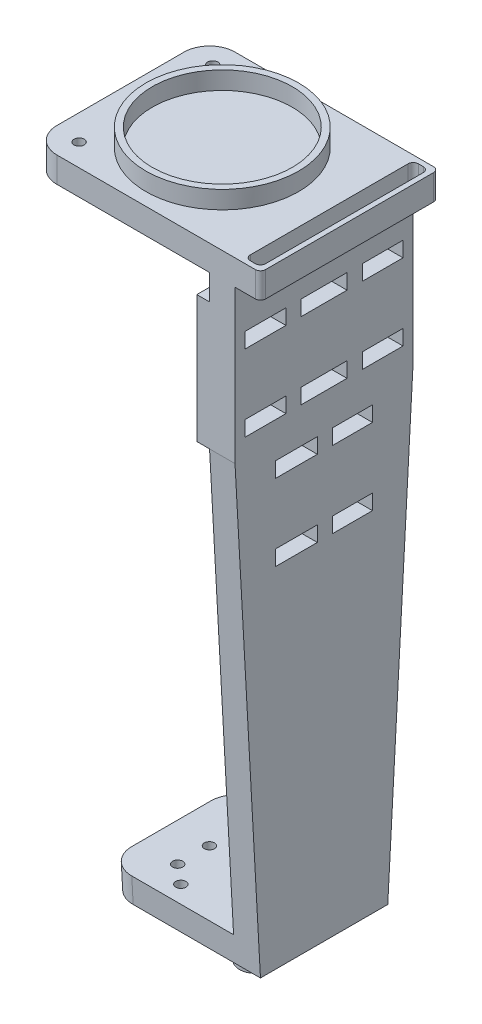
SolidWorks part; units mm, degrees
ref_plane "Front Plane" through (0, 0, 0) normal (0, 0, 1) x (1, 0, 0)
ref_plane "Top Plane" through (0, 0, 0) normal (0, 1, 0) x (1, 0, 0)
ref_plane "Right Plane" through (0, 0, 0) normal (1, 0, 0) x (0, 0, -1)
sketch "Sketch1" plane through (0, 0, 0) normal (0, 1, 0) x (1, 0, 0)
  line L1 (0, 0) -> (-80, 0)
  line L2 (0, 0) -> (0, -70)
  line L3 (0, -70) -> (-80, -70)
  line L4 (-80, 0) -> (-80, -70)
  dimension "D1" = 80
  dimension "D2" = 70
extrude "Boss-Extrude1" add sketch "Sketch1" along normal blind 10
sketch "Sketch2" plane through (0, 0, 0) normal (0, -1, 0) x (1, 0, 0)
  line L0 (0, 0) -> (-80, 0) construction
  line L1 (0, 70) -> (-10, 70)
  line L2 (0, 70) -> (0, 0)
  line L3 (0, 0) -> (-10, 0)
  line L4 (-10, 70) -> (-10, 0)
  dimension "D1" = 10
extrude "Boss-Extrude2" add sketch "Sketch2" along normal blind 450
sketch "Sketch3" plane through (0, 10, 0) normal (0, 1, 0) x (1, 0, 0)
  line L0 (0, 0) -> (-80, -70) construction
  line L1 (-80, -70) -> (-80, 0) construction
  line L2 (-80, 0) -> (0, -70) construction
  line L3 (0, -70) -> (0, 0) construction
  line L4 (0, 0) -> (-80, 0) construction
  line L5 (-80, 0) -> (-80, -70) construction
  line L6 (-80, -70) -> (0, -70) construction
  circle A0 centre (-40, -35) radius 27.5
  circle A1 centre (-40, -35) radius 30
  dimension "D1" = 55
  dimension "D2" = 60
extrude "Boss-Extrude3" add sketch "Sketch3" along normal blind 7
sketch "Sketch6" plane through (0, 10, 0) normal (0, 1, 0) x (1, 0, 0)
  line L0 (-80, -70) -> (-80, -35) construction
  line L1 (-80, 0) -> (-80, -70) construction
  line L2 (-80, -35) -> (-40, -70) construction
  line L3 (-80, -70) -> (0, -70) construction
  line L4 (-40, -70) -> (-80, -70) construction
  line L5 (-80, -70) -> (-80, -35) construction
  line L6 (-80, -35) -> (-80, 0) construction
  line L7 (-80, 0) -> (-40, 0) construction
  line L8 (0, 0) -> (-80, 0) construction
  line L9 (-40, 0) -> (-80, -35) construction
  line L10 (-80, -52.5) -> (-60, -70) construction
  line L11 (-80, -17.5) -> (-60, 0) construction
  circle A0 centre (-70, -61.25) radius 2
  circle A1 centre (-70, -8.75) radius 2
  dimension "D1" = 4
  dimension "D2" = 4
extrude "Cut-Extrude3" cut sketch "Sketch6" against normal blind 27
sketch "Sketch7" plane through (-10, 0, 0) normal (-1, 0, 0) x (0, 0, 1)
  line L0 (70, -450) -> (70, 0) construction
  line L1 (0, -450) -> (70, -450)
  line L2 (0, -450) -> (0, -240)
  line L3 (0, -240) -> (70, -240)
  line L4 (70, -450) -> (70, -240)
  dimension "D1" = 210
extrude "Cut-Extrude4" cut sketch "Sketch7" against normal blind 27
sketch "Sketch10" plane through (-10, 0, 0) normal (-1, 0, 0) x (0, 0, 1)
  line L0 (0, 0) -> (0, -120) construction
  line L1 (0, -240) -> (0, 0) construction
  line L2 (0, -120) -> (70, -120) construction
  line L3 (70, -240) -> (70, 0) construction
  line L4 (70, -120) -> (70, 0) construction
  line L5 (70, 0) -> (0, 0) construction
  line L6 (0, 0) -> (70, -120) construction
  line L7 (70, 0) -> (0, -120) construction
  line L8 (0, -240) -> (70, -240) construction
  line L9 (70, -240) -> (35, -240) construction
  line L10 (35, -240) -> (0, -240) construction
  line L11 (0, -60) -> (10, -240)
  line L12 (0, -240) -> (0, -60)
  line L13 (70, -60) -> (60, -240)
  line L14 (60, -240) -> (70, -240)
  line L15 (70, -240) -> (70, -60)
  line L16 (0, -240) -> (10, -240)
  dimension "D1" = 10
  dimension "D2" = 10
extrude "Cut-Extrude5" cut sketch "Sketch10" against normal blind 70
sketch "Sketch11" plane through (-10, 0, 0) normal (-1, 0, 0) x (0, 0, 1)
  line L0 (10.1166, -240) -> (60, -240)
  line L1 (60, -240) -> (10, -240) construction
  line L2 (60, -240) -> (60.5556, -230)
  line L3 (70, -60) -> (60, -240) construction
  line L4 (60.5556, -230) -> (9.4444, -230)
  line L5 (10, -240) -> (0, -60) construction
  line L6 (9.4444, -230) -> (10.1166, -240)
  dimension "D1" = 10
extrude "Boss-Extrude5" add sketch "Sketch11" along normal blind 50
sketch "Sketch12" plane through (0, -240, 0) normal (0, -1, 0) x (1, 0, 0)
  line L0 (-60, 60) -> (0, 10) construction
  line L1 (0, 10) -> (0, 60) construction
  line L2 (0, 60) -> (-60, 10.1166) construction
  circle A0 centre (-30, 35) radius 7.5
  circle A1 centre (-30, 35) radius 10
  circle A2 centre (-30, 35) radius 2.5
  dimension "D1" = 15
  dimension "D2" = 20
  dimension "D3" = 5
extrude "Boss-Extrude6" add sketch "Sketch12" along normal blind 25 contours A2 | A1 A0 region at (-39.7172, -240, 35) region at (-30, -240, 35)
sketch "Sketch13" plane through (0, -240, 0) normal (0, -1, 0) x (-1, 0, 0)
  line L0 (60, -60) -> (0, -60) construction
  line L1 (0, -60) -> (0, -10) construction
  line L2 (0, -10) -> (60, -10.1166) construction
  line L3 (60, -10.1166) -> (60, -60) construction
  line L4 (60, -60) -> (30, -60) construction
  line L5 (30, -60) -> (0, -60) construction
  line L6 (0, -60) -> (0, -35) construction
  line L7 (0, -35) -> (0, -10) construction
  line L8 (0, -10) -> (30, -10.0583) construction
  line L9 (30, -10.0583) -> (60, -10.1166) construction
  line L10 (60, -10.1166) -> (60, -35.0583) construction
  line L11 (60, -35.0583) -> (60, -60) construction
  line L12 (60, -35.0583) -> (30, -60) construction
  line L13 (30, -60) -> (0, -35) construction
  line L14 (0, -35) -> (30, -10.0583) construction
  line L15 (30, -10.0583) -> (60, -35.0583) construction
  line L16 (45, -47.5291) -> (45, -60) construction
  line L17 (45, -60) -> (45, -10.0874) construction
  line L18 (45, -47.5291) -> (15, -47.5) construction
  line L19 (15, -47.5) -> (15, -22.5291) construction
  line L20 (15, -22.5291) -> (45, -22.5583) construction
  line L21 (45, -47.5291) -> (30, -60) construction
  line L22 (30, -60) -> (45, -47.5291) construction
  line L23 (45, -47.5291) -> (37.5, -53.7646) construction
  line L24 (37.5, -53.7646) -> (37.5, -16.3083) construction
  circle A0 centre (45, -47.5291) radius 2
  circle A1 centre (45, -22.5583) radius 2
  circle A2 centre (45, -35.0437) radius 2
  circle A3 centre (37.5, -53.7646) radius 2
  circle A4 centre (37.5, -16.3083) radius 2
  dimension "D1" = 4
  dimension "D2" = 4
  dimension "D3" = 4
  dimension "D4" = 4
  dimension "D5" = 4
extrude "Cut-Extrude6" cut sketch "Sketch13" against normal blind 25
sketch "Sketch14" plane through (-10, 0, 0) normal (-1, 0, 0) x (0, 0, 1)
  line L1 (0, -60) -> (24, -60)
  line L2 (0, -60) -> (0, -10)
  line L3 (0, -10) -> (24, -10)
  line L4 (24, -60) -> (24, -10)
  line L5 (2, -12) -> (22, -12)
  line L6 (2, -12) -> (2, -58)
  line L7 (2, -58) -> (22, -58)
  line L8 (22, -12) -> (22, -58)
  dimension "D1" = 50
  dimension "D2" = 24
  dimension "D3" = 2
  dimension "D4" = 2
  dimension "D5" = 2
  dimension "D6" = 2
extrude "Boss-Extrude7" add sketch "Sketch14" along normal blind 5
sketch "Sketch15" plane through (-10, 0, 0) normal (-1, 0, 0) x (0, 0, 1)
  line L1 (70, -60) -> (46, -60)
  line L2 (70, -60) -> (70, -10)
  line L3 (70, -10) -> (46, -10)
  line L4 (46, -60) -> (46, -10)
  line L5 (68, -58) -> (48, -58)
  line L6 (68, -58) -> (68, -12)
  line L7 (68, -12) -> (48, -12)
  line L8 (48, -58) -> (48, -12)
  dimension "D1" = 50
  dimension "D2" = 24
  dimension "D3" = 2
  dimension "D4" = 2
  dimension "D5" = 2
  dimension "D6" = 2
extrude "Boss-Extrude8" add sketch "Sketch15" along normal blind 5
sketch "Sketch16" plane through (-10, 0, 0) normal (-1, 0, 0) x (0, 0, 1)
  line L1 (24, -10) -> (46, -10)
  line L2 (24, -10) -> (24, -60)
  line L3 (24, -60) -> (46, -60)
  line L4 (46, -10) -> (46, -60)
  line L5 (24, -12) -> (46, -12)
  line L6 (24, -12) -> (24, -58)
  line L7 (24, -58) -> (46, -58)
  line L8 (46, -12) -> (46, -58)
  line M6 (24, -10) -> (24, -60)
  line M12 (46, -60) -> (46, -10)
  dimension "D1" = 2
  dimension "D2" = 2
extrude "Boss-Extrude9" add sketch "Sketch16" along normal blind 5 contours L5 L4 L1 M6 | L7 L3 M6 M12 region at (-10, -11, 35) region at (-10, -59, 35)
sketch "Sketch17" plane through (-10, 0, 0) normal (-1, 0, 0) x (0, 0, 1)
  line L0 (0, -60) -> (70, -60) construction
  line L1 (70, -60) -> (35, -60) construction
  line L2 (35, -60) -> (0, -60) construction
  line L3 (12, -12) -> (12, -60) construction
  line L4 (22, -12) -> (2, -12) construction
  line L5 (58, -12) -> (58, -60) construction
  line L6 (68, -12) -> (48, -12) construction
  line L7 (12, -60) -> (58, -60)
  line L8 (58, -60) -> (58, -110)
  line L9 (58, -110) -> (12, -110)
  line L10 (12, -110) -> (12, -60)
  line L12 (14, -62) -> (33.659, -62)
  line L13 (14, -62) -> (14, -108)
  line L14 (14, -108) -> (33.659, -108)
  line L15 (33.659, -62) -> (33.659, -108)
  line L16 (35.659, -62) -> (56, -62)
  line L17 (35.659, -62) -> (35.659, -108)
  line L18 (35.659, -108) -> (56, -108)
  line L19 (56, -62) -> (56, -108)
  dimension "D1" = 50
  dimension "D2" = 2
  dimension "D3" = 2
  dimension "D4" = 2
  dimension "D5" = 2
  dimension "D6" = 2
  dimension "D7" = 2
  dimension "D8" = 2
extrude "Boss-Extrude10" add sketch "Sketch17" along normal blind 5
sketch "Sketch18" plane through (-10, 0, 0) normal (-1, 0, 0) x (0, 0, 1)
  line L0 (2, -12) -> (2, -58) construction
  line L1 (4, -17) -> (20, -17)
  line L2 (4, -17) -> (4, -23)
  line L3 (4, -23) -> (20, -23)
  line L4 (20, -17) -> (20, -23)
  line L5 (26, -17) -> (44, -17)
  line L6 (26, -17) -> (26, -23)
  line L7 (26, -23) -> (44, -23)
  line L8 (44, -17) -> (44, -23)
  line L9 (50, -17) -> (66, -17)
  line L10 (50, -17) -> (50, -23)
  line L11 (50, -23) -> (66, -23)
  line L12 (66, -17) -> (66, -23)
  line L13 (4, -47) -> (20, -47)
  line L14 (4, -47) -> (4, -53)
  line L15 (4, -53) -> (20, -53)
  line L16 (20, -47) -> (20, -53)
  line L17 (26, -47) -> (44, -47)
  line L18 (26, -47) -> (26, -53)
  line L19 (26, -53) -> (44, -53)
  line L20 (44, -47) -> (44, -53)
  line L21 (50, -47) -> (66, -47)
  line L22 (50, -47) -> (50, -53)
  line L23 (50, -53) -> (66, -53)
  line L24 (66, -47) -> (66, -53)
  line L25 (22, -58) -> (22, -12) construction
  line L26 (22, -12) -> (2, -12) construction
  line L27 (2, -58) -> (22, -58) construction
  line L28 (24, -58) -> (24, -12) construction
  line L29 (24, -12) -> (46, -12) construction
  line L30 (24, -58) -> (46, -58) construction
  line L31 (48, -58) -> (68, -58) construction
  line L32 (68, -12) -> (48, -12) construction
  line L33 (46, -12) -> (46, -58) construction
  line L34 (68, -58) -> (68, -12) construction
  line L35 (48, -12) -> (48, -58) construction
  point P28 (12, -12)
  dimension "D1" = 2
  dimension "D2" = 2
  dimension "D3" = 5
  dimension "D4" = 35
  dimension "D5" = 2
  dimension "D6" = 5
  dimension "D7" = 35
  dimension "D8" = 35
  dimension "D9" = 5
  dimension "D10" = 2
  dimension "D11" = 2
  dimension "D12" = 2
  dimension "D13" = 2
  dimension "D14" = 2
  dimension "D15" = 2
  dimension "D16" = 2
  dimension "D17" = 2
  dimension "D18" = 2
  dimension "D19" = 5
  dimension "D20" = 5
  dimension "D21" = 5
  dimension "D22" = 35
  dimension "D23" = 35
  dimension "D24" = 35
extrude "Cut-Extrude8" cut sketch "Sketch18" against normal blind 10
sketch "Sketch19" plane through (-10, 0, 0) normal (-1, 0, 0) x (0, 0, 1)
  line L0 (14, -62) -> (14, -108) construction
  line L1 (16, -67) -> (31.659, -67)
  line L2 (16, -67) -> (16, -73)
  line L3 (16, -73) -> (31.659, -73)
  line L4 (31.659, -67) -> (31.659, -73)
  line L5 (16, -97) -> (31.659, -97)
  line L6 (16, -97) -> (16, -103)
  line L7 (16, -103) -> (31.659, -103)
  line L8 (31.659, -97) -> (31.659, -103)
  line L9 (37.659, -67) -> (54, -67)
  line L10 (37.659, -67) -> (37.659, -73)
  line L11 (37.659, -73) -> (54, -73)
  line L12 (54, -67) -> (54, -73)
  line L13 (37.659, -97) -> (54, -97)
  line L14 (37.659, -97) -> (37.659, -103)
  line L15 (37.659, -103) -> (54, -103)
  line L16 (54, -97) -> (54, -103)
  line L17 (35.659, -62) -> (35.659, -108) construction
  line L18 (33.659, -62) -> (14, -62) construction
  line L19 (56, -62) -> (35.659, -62) construction
  line L20 (14, -108) -> (33.659, -108) construction
  line L21 (35.659, -108) -> (56, -108) construction
  line L22 (33.659, -108) -> (33.659, -62) construction
  line L23 (56, -108) -> (56, -62) construction
  dimension "D1" = 2
  dimension "D2" = 2
  dimension "D3" = 2
  dimension "D4" = 2
  dimension "D5" = 5
  dimension "D6" = 5
  dimension "D7" = 35
  dimension "D8" = 35
  dimension "D9" = 5
  dimension "D10" = 5
  dimension "D11" = 2
  dimension "D12" = 2
  dimension "D13" = 2
  dimension "D14" = 2
  dimension "D15" = 35
  dimension "D16" = 35
extrude "Cut-Extrude9" cut sketch "Sketch19" against normal blind 10
fillet "Fillet1" radius 10 2 edges at (-80, 5, 0) (-80, 5, 70)
fillet "Fillet2" radius 10 2 edges at (-60, -235, 60.2778) (-60, -235, 9.7805)
sketch "Sketch20" plane through (0, 0, 0) normal (1, 0, 0) x (0, 0, -1)
  line L1 (-70, 10) -> (0, 10)
  line L2 (-70, 10) -> (-70, 0)
  line L3 (-70, 0) -> (0, 0)
  line L4 (0, 10) -> (0, 0)
extrude "Boss-Extrude11" add sketch "Sketch20" along normal blind 10
sketch "Sketch21" plane through (0, 0, 0) normal (0, -1, 0) x (1, 0, 0)
  line L0 (10, 70) -> (10, 0) construction
  line L1 (2, 68) -> (8, 68)
  line L2 (2, 68) -> (2, 2)
  line L3 (2, 2) -> (8, 2)
  line L4 (8, 68) -> (8, 2)
  line L5 (0, 70) -> (0, 0) construction
  line L6 (10, 70) -> (0, 70) construction
  line L7 (10, 0) -> (0, 0) construction
  dimension "D1" = 2
  dimension "D2" = 2
  dimension "D3" = 2
  dimension "D4" = 2
extrude "Cut-Extrude10" cut sketch "Sketch21" against normal blind 10
fillet "Fillet3" radius 2 2 edges at (10, 5, 70) (10, 5, 0)
fillet "Fillet4" radius 2 2 edges at (8, 5, 2) (8, 5, 68)
fillet "Fillet5" radius 2 2 edges at (2, 5, 2) (2, 5, 68)
sketch "Sketch23" plane through (0, -240, 0) normal (0, -1, 0) x (1, 0, 0)
  line L1 (-41.5076, 24.2648) -> (-16.34, 24.2648)
  line L2 (-41.5076, 24.2648) -> (-41.5076, 49.9927)
  line L3 (-41.5076, 49.9927) -> (-16.34, 49.9927)
  line L4 (-16.34, 24.2648) -> (-16.34, 49.9927)
extrude "Cut-Extrude12" cut sketch "Sketch23" along normal blind 116
sketch "Sketch25" plane through (0, -240, 0) normal (0, -1, 0) x (-1, 0, 0)
  line L0 (0, -10) -> (0, -60) construction
  circle A0 centre (26.9951, -35) radius 6.25
  dimension "D1" = 12.5
extrude "Boss-Extrude12" add sketch "Sketch25" along normal blind 15
sketch "Sketch26" plane through (0, -255, 0) normal (0, -1, 0) x (-1, 0, 0)
  line L0 (33.2451, -35) -> (20.7451, -35) construction
  line L2 (20.7451, -10) -> (33.2451, -10)
  line L3 (20.7451, -10) -> (20.7451, -60)
  line L4 (20.7451, -60) -> (33.2451, -60)
  line L5 (33.2451, -10) -> (33.2451, -60)
  line L6 (20.7451, -10) -> (33.2451, -60) construction
  line L7 (20.7451, -60) -> (33.2451, -10) construction
  line L8 (33.2451, -10) -> (20.7451, -10)
  line L9 (33.2451, -10) -> (33.2451, -14)
  line L10 (33.2451, -14) -> (20.7451, -14)
  line L11 (20.7451, -10) -> (20.7451, -14)
  line L12 (33.2451, -60) -> (20.7451, -60)
  line L13 (33.2451, -60) -> (33.2451, -56)
  line L14 (33.2451, -56) -> (20.7451, -56)
  line L15 (20.7451, -60) -> (20.7451, -56)
  circle A0 centre (26.9951, -35) radius 6.25 construction
  point P5 (26.9951, -35)
  dimension "D1" = 50
  dimension "D2" = 4
  dimension "D3" = 4
extrude "Boss-Extrude13" add sketch "Sketch26" along normal blind 10 contours L10 L5 L2 L3 | L14 L5 L0 L3 | L5 L10 L3 L0 | L0 | L5 L14 L3 L4 region at (-26.9951, -255, 45.5) region at (-26.9951, -255, 24.5) region at (-26.9951, -255, 12) region at (-26.9951, -255, 58)
sketch "Sketch27" plane through (0, -265, 0) normal (0, -1, 0) x (1, 0, 0)
  line L0 (-20.7451, 10) -> (-20.7451, 60) construction
  line L1 (-33.2451, 10) -> (-20.7451, 10)
  line L2 (-33.2451, 10) -> (-33.2451, 15)
  line L3 (-33.2451, 15) -> (-20.7451, 15)
  line L4 (-20.7451, 10) -> (-20.7451, 15)
  line L6 (-33.2451, 60) -> (-20.7451, 60)
  line L7 (-33.2451, 60) -> (-33.2451, 55)
  line L8 (-33.2451, 55) -> (-20.7451, 55)
  line L9 (-20.7451, 60) -> (-20.7451, 55)
  dimension "D1" = 5
  dimension "D2" = 5
extrude "Boss-Extrude15" add sketch "Sketch27" along normal blind 12.5
fillet "Fillet8" radius 6.25 4 edges at (-20.7451, -277.5, 57.5) (-33.2451, -277.5, 57.5) (-20.7451, -277.5, 12.5) (-33.2451, -277.5, 12.5)
sketch "Sketch29" plane through (0, 0, 55) normal (0, 0, -1) x (-1, 0, 0)
  line L0 (26.9951, -277.5) -> (26.9951, -265) construction
  line L1 (33.2451, -265) -> (20.7451, -265) construction
  circle A0 centre (26.9951, -271.25) radius 2.5
  dimension "D1" = 5
extrude "Cut-Extrude14" cut sketch "Sketch29" against normal blind 12.5 and the other way blind 52.5
fillet "Fillet9" radius 6.25 4 edges at (-20.7451, -255, 47.5) (-33.2451, -255, 47.5) (-20.7451, -255, 22.5) (-33.2451, -255, 22.5)
sketch "Sketch30" plane through (0, 0, 10) normal (0, 0, -1) x (-1, 0, 0)
  line L1 (38.1602, -252.0174) -> (14.7242, -252.0174)
  line L2 (38.1602, -252.0174) -> (38.1602, -283.1402)
  line L3 (38.1602, -283.1402) -> (14.7242, -283.1402)
  line L4 (14.7242, -252.0174) -> (14.7242, -283.1402)
extrude "Cut-Extrude15" cut sketch "Sketch30" against normal blind 78
sketch "Sketch31" plane through (0, -252.0174, 0) normal (0, -1, 0) x (1, 0, 0)
  circle A0 centre (-26.9951, 35) radius 6.25
extrude "Boss-Extrude16" add sketch "Sketch31" along normal blind 8 and the other way blind 12
sketch "Sketch32" plane through (0, -260.0174, 0) normal (0, -1, 0) x (-1, 0, 0)
  circle A0 centre (26.9951, -35) radius 5
  dimension "D1" = 10
extrude "Cut-Extrude16" cut sketch "Sketch32" against normal blind 20
sketch "Sketch33" plane through (0, -240.0174, 0) normal (0, -1, 0) x (1, 0, 0)
  circle A0 centre (-26.9951, 35) radius 2.5
  dimension "D1" = 5
extrude "Boss-Extrude17" add sketch "Sketch33" along normal blind 20
